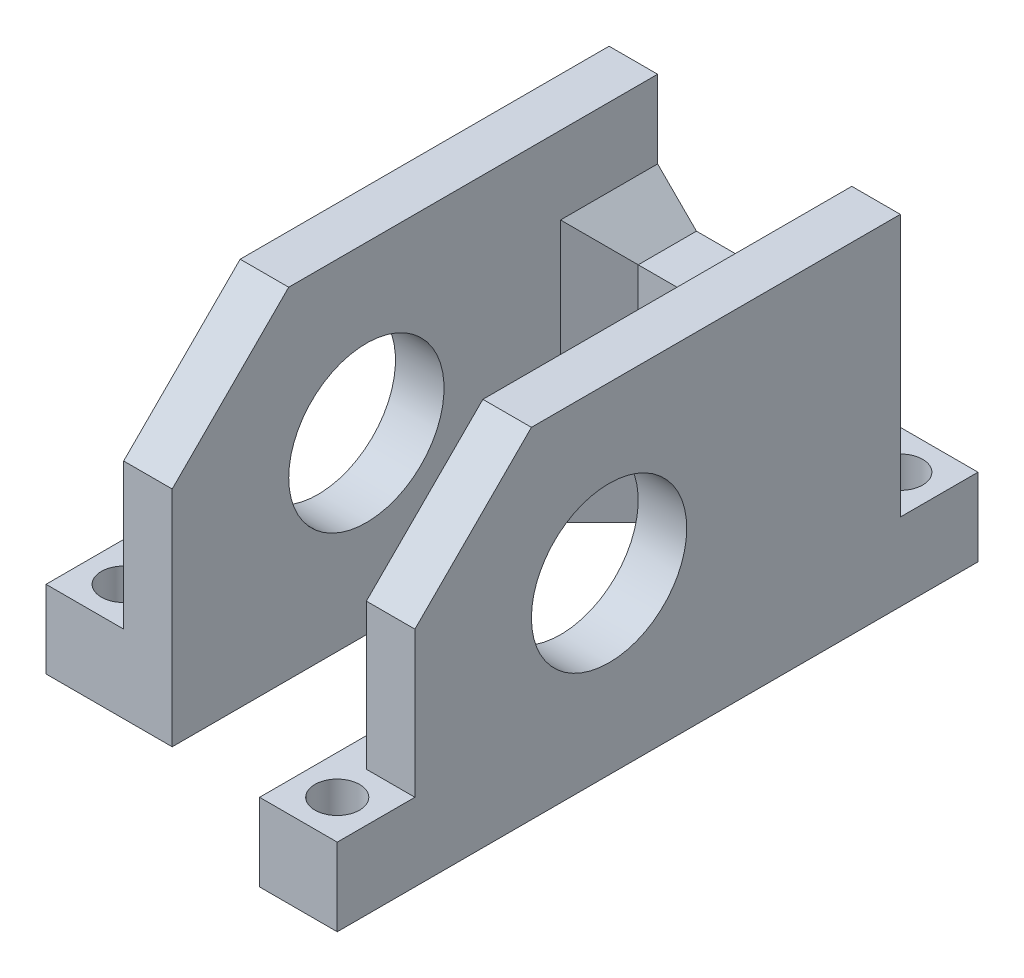
SolidWorks part; units mm, degrees
ref_plane "Plan de face" through (0, 0, 0) normal (0, 0, 1) x (1, 0, 0)
ref_plane "Plan de dessus" through (0, 0, 0) normal (0, 1, 0) x (1, 0, 0)
ref_plane "Plan de droite" through (0, 0, 0) normal (1, 0, 0) x (0, 0, -1)
sketch "Esquisse1" plane through (0, 0, 0) normal (0, 1, 0) x (1, 0, 0)
  line L8 (-23, 9) -> (-23, -41)
  line L9 (-18, 9) -> (-23, 9)
  line L28 (-23, -41) -> (-18, -41)
  line L30 (-18, -41) -> (-18, 3)
  line L31 (7, 3) -> (7, -41)
  line L32 (7, -41) -> (2, -41)
  line L33 (2, -41) -> (2, 3)
  line L35 (-18, 9) -> (2, 9)
  line L38 (-18, 3) -> (2, 3)
  line L39 (-23, -41) -> (-31, -41)
  line L40 (-31, -41) -> (-31, -33)
  line L45 (7, 9) -> (7, 3)
  line L46 (7, 3) -> (-23, 3) construction
  line L47 (-23, 3) -> (-23, 9)
  line L50 (-31, -33) -> (-23, -33)
  line L51 (2, 9) -> (7, 9)
  line L55 (-31, -33) -> (-23, -41) construction
  line L56 (-23, -33) -> (-31, -41) construction
  line L57 (-23, 9) -> (-31, 9)
  line L58 (7, 9) -> (7, 17)
  line L59 (7, 17) -> (-1, 17)
  line L60 (-1, 17) -> (-1, 9)
  line L61 (-1, 9) -> (7, 17) construction
  line L62 (-1, 17) -> (7, 9) construction
  line L63 (7, -41) -> (7, -49)
  line L64 (7, -49) -> (-1, -49)
  line L65 (-1, -49) -> (-1, -37)
  line L66 (-1, -37) -> (2, -37)
  line L67 (7, -49) -> (-1, -41) construction
  line L68 (-1, -41) -> (-1, -49) construction
  line L69 (7, -41) -> (-1, -49) construction
  line L70 (-31, 9) -> (-31, 1)
  line L71 (-31, 1) -> (-23, 1)
  line L72 (-31, 9) -> (-23, 1) construction
  line L73 (-23, 1) -> (-23, 9) construction
  line L74 (-31, 1) -> (-23, 9) construction
  circle A8 centre (3, 13) radius 2.3
  circle A10 centre (3, -45) radius 2.3
  circle A11 centre (-27, -37) radius 2.3
  circle A12 centre (-27, 5) radius 2.3
extrude "Boss.-Extru.1" add sketch "Esquisse1" along normal blind 35 contours L46 | L46 L9 | L46 L35 | L51 L46 region at (-20.5, 0, -8.4169)
extrude "Boss.-Extru.7" add sketch "Esquisse1<6>" along normal blind 8 contours L28 region at (-20.5, 0, -8.4169)
sketch "Esquisse1<6>" plane through (0, 0, 0) normal (0, 1, 0) x (1, 0, 0) same geometry as "Esquisse1"
extrude "Boss.-Extru.8" add sketch "Esquisse1<8>" along normal blind 8 contours L59 L60 L35 L51 L58 A8 | L30 L28 L40 | L66 L65 L64 L63 L32 L33 A10 | L50 L40 L39 L8 A11 | L70 L71 L8 L57 A12 region at (-23.1131, 0, -6) region at (-0.8869, 0, -13) region at (-23.1131, 0, 37) region at (6.8558, 0, 45)
sketch "Esquisse1<8>" plane through (0, 0, 0) normal (0, 1, 0) x (1, 0, 0) same geometry as "Esquisse1"
sketch "Esquisse6" plane through (0, 0, 0) normal (0, -1, 0) x (1, 0, 0)
  line L0 (-18, -3) -> (-14, -3)
  line L1 (-18, -3) -> (2, -3) construction
  line L2 (-18, -3) -> (-18, 1)
  line L3 (-18, 41) -> (-18, -3) construction
  line L4 (-18, 1) -> (-14, -3)
  line L5 (2, -3) -> (-2, -3)
  line L6 (-2, -3) -> (2, 1)
  line L7 (2, 37) -> (2, -3) construction
  line L8 (2, 1) -> (2, -3)
extrude "Boss.-Extru.9" add sketch "Esquisse6" against normal blind 35
sketch "Esquisse7" plane through (0, 0, -9) normal (0, 0, -1) x (-1, 0, 0)
  line L0 (-7, 35) -> (-2, 35) construction
  line L3 (18, 23) -> (14, 23) construction
  line L8 (-2, 23) -> (2, 23) construction
  line L9 (2, 23) -> (-2, 23) construction
  line L10 (-2, 23) -> (-2, 27) construction
  line L14 (-2, 35) -> (18, 35)
  line L16 (18, 23) -> (18, 27) construction
  line L17 (2, 23) -> (14, 23)
  line L18 (-2, 27) -> (2, 23)
  line L24 (-2, 27) -> (-2, 35)
  line L25 (18, 23) -> (18, 35)
  line L26 (18, 27) -> (14, 23)
  line M8 (23, 35) -> (-7, 35)
extrude "Enlèv. mat.-Extru.5" cut sketch "Esquisse7" against normal blind 35 contours L18 M8 region at (-8, 29.3333, -9)
sketch "Esquisse8" plane through (-23, 0, 0) normal (-1, 0, 0) x (0, 0, 1)
  line L0 (41, 0) -> (21, 0) construction
  line L1 (-1, 0) -> (33, 0) construction
  line L2 (21, 0) -> (21, 18) construction
  line L3 (41, 35) -> (41, 23)
  line L4 (41, 35) -> (41, 8) construction
  line L5 (41, 23) -> (41, 35)
  line L6 (41, 35) -> (29, 35)
  line L7 (-9, 35) -> (41, 35) construction
  line L8 (29, 35) -> (41, 23)
  circle A0 centre (21, 18) radius 8
  line M3 (41, 8) -> (41, 35)
  line M4 (41, 35) -> (-9, 35)
extrude "Enlèv. mat.-Extru.6" cut sketch "Esquisse8" against normal blind 50 contours A0 | L8 M4 M3 region at (-23, 31, 37) region at (-23, 18, 21)
